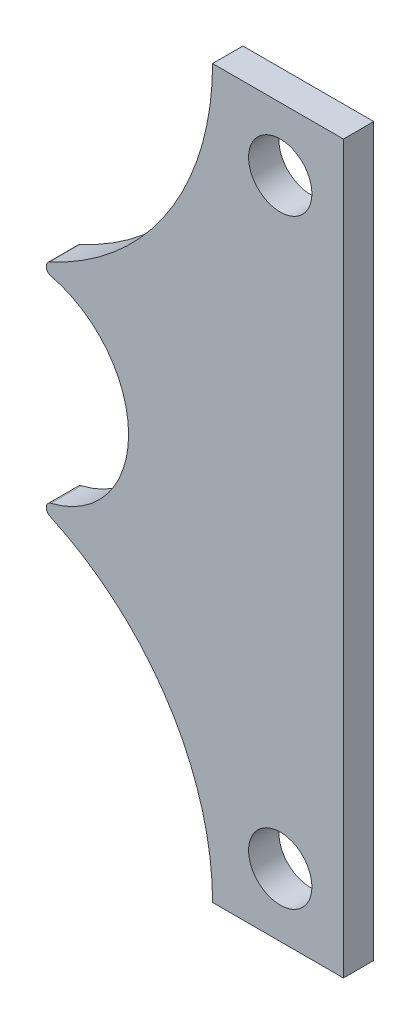
SolidWorks part; units mm, degrees
ref_plane "Front Plane" through (0, 0, 0) normal (0, 0, 1) x (1, 0, 0)
ref_plane "Top Plane" through (0, 0, 0) normal (0, 1, 0) x (1, 0, 0)
ref_plane "Right Plane" through (0, 0, 0) normal (1, 0, 0) x (0, 0, -1)
sketch "Sketch1" plane through (0, 0, 0) normal (0, 0, 1) x (1, 0, 0)
  line L0 (-7.2461, 73.025) -> (-7.2461, -73.025) construction
  line L1 (-19.05, -73.025) -> (19.05, -73.025)
  line L2 (-19.05, -73.025) -> (-19.05, 73.025)
  line L3 (-19.05, 73.025) -> (19.05, 73.025)
  line L4 (19.05, -73.025) -> (19.05, 73.025)
  line L5 (-19.05, -73.025) -> (19.05, 73.025) construction
  line L6 (-19.05, 73.025) -> (19.05, -73.025) construction
  line L7 (-44.45, 20.32) -> (-44.45, -20.32) construction
  line L8 (-44.45, 0) -> (0, 0) construction
  circle A0 centre (-44.45, 0) radius 52.07
  circle A1 centre (6.35, 60.325) radius 6.3627
  circle A2 centre (6.35, -60.325) radius 6.3627
  arc A3 (-7.2461, 73.025) -> (-19.05, 45.4546) centre (-45.3461, 73.025) cw
  circle A4 centre (-44.45, 0) radius 20.32
  arc A5 (-7.2461, 73.025) -> (-44.45, 20.32) centre (-63.1804, 73.025) cw
  arc A6 (-7.2461, -73.025) -> (-44.45, -20.32) centre (-63.1804, -73.025) ccw
  point P0 (0, 0)
  dimension "D2" = 104.14
  dimension "D3" = 12.7254
  dimension "D9" = 38.1
  dimension "D10" = 40.64
  dimension "D1" = 146.05
  dimension "D4" = 12.7
  dimension "D5" = 12.7
  dimension "D6" = 50.8
  dimension "D7" = 38.1
  dimension "D8" = 12.7
extrude "Boss-Extrude1" add sketch "Sketch1" along normal mid plane 6.096 contours A6 L2 A5 A4 | A6 A0 A5 L2 | A6 L1 L4 L3 A5 A0 A2 A1 region at (-7.9628, -57.2179, 0) region at (-7.9713, 0, 0) region at (-29.9637, -27.0142, 0)
fillet "Fillet1" radius 1.27 2 edges at (-44.45, -20.32, 0) (-44.45, 20.32, 0)
